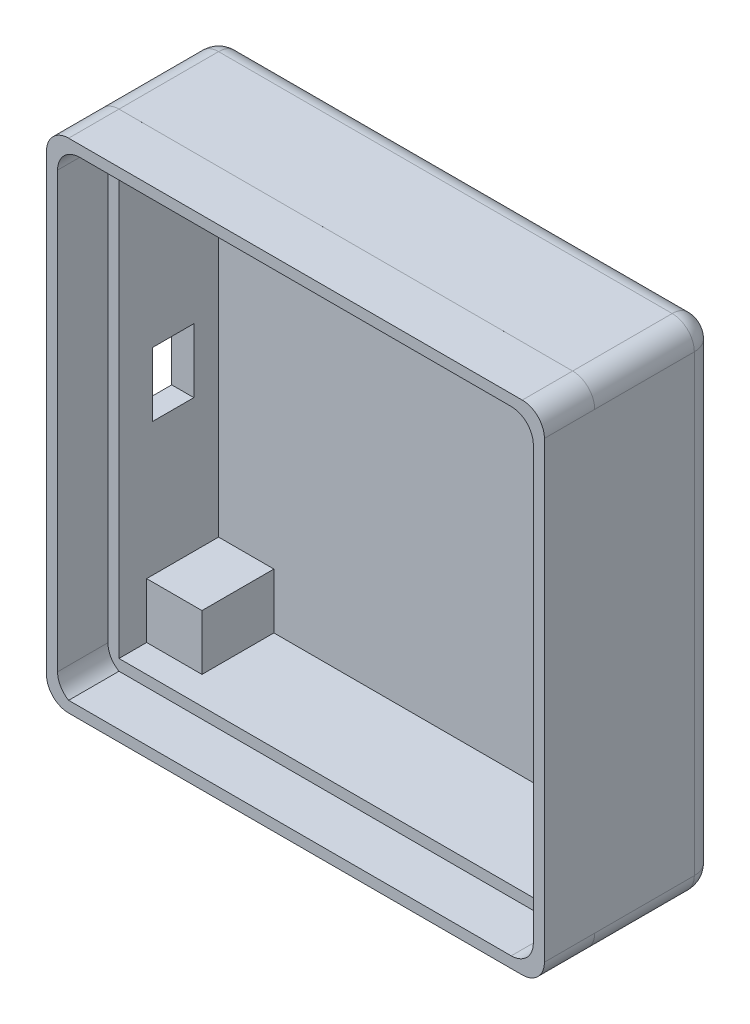
SolidWorks part; units mm, degrees
ref_plane "Piano frontale" through (0, 0, 0) normal (0, 0, 1) x (1, 0, 0)
ref_plane "Piano superiore" through (0, 0, 0) normal (0, 1, 0) x (1, 0, 0)
ref_plane "Piano destro" through (0, 0, 0) normal (1, 0, 0) x (0, 0, -1)
sketch "Schizzo2" plane through (0, 0, 0) normal (0, 0, 1) x (1, 0, 0)
  line L1 (0, 0) -> (45, 0)
  line L2 (0, 0) -> (0, 45)
  line L3 (0, 45) -> (45, 45)
  line L4 (45, 0) -> (45, 45)
  dimension "D1" = 45
  dimension "D2" = 45
extrude "Estrusione-Estrusione2" add sketch "Schizzo2" along normal blind 11
shell "Svuota1" thickness 2 removed face at (22.5, 22.5, 11)
fillet "Raccordo1" radius 2 4 edges at (45, 45, 5.5) (45, 0, 5.5) (0, 0, 5.5) (0, 45, 5.5)
fillet "Raccordo2" radius 2 8 edges at (44.4142, 0.5858, 0) (22.5, 0, 0) (0.5858, 0.5858, 0) (0, 22.5, 0) (0.5858, 44.4142, 0) (22.5, 45, 0) (44.4142, 44.4142, 0) (45, 22.5, 0)
sketch "Schizzo3" plane through (0, 0, 2) normal (0, 0, 1) x (1, 0, 0)
  line L0 (43, 43) -> (2, 43) construction
  line L1 (2, 43) -> (7, 43)
  line L2 (2, 43) -> (2, 38)
  line L3 (2, 38) -> (7, 38)
  line L4 (7, 43) -> (7, 38)
  line L5 (43, 43) -> (2, 43) construction
  dimension "D1" = 5
  dimension "D2" = 5
extrude "Estrusione-Estrusione3" add sketch "Schizzo3" along normal blind 6.5
sketch "Schizzo4" plane through (0, 0, 2) normal (0, 0, 1) x (1, 0, 0)
  line L1 (43, 2) -> (38, 2)
  line L2 (43, 2) -> (43, 7)
  line L3 (43, 7) -> (38, 7)
  line L4 (38, 2) -> (38, 7)
  dimension "D1" = 5
  dimension "D2" = 5
extrude "Estrusione-Estrusione4" add sketch "Schizzo4" along normal blind 6.5
fillet "Raccordo3" radius 4 2 edges at (38, 7, 5.25) (7, 38, 5.25)
sketch "Schizzo5" plane through (0, 0, 2) normal (0, 0, 1) x (1, 0, 0)
  line L0 (43, 2) -> (43, 43) construction
  line L1 (43, 43) -> (38, 43)
  line L2 (43, 43) -> (43, 38)
  line L3 (43, 38) -> (38, 38)
  line L4 (38, 43) -> (38, 38)
  line L5 (43, 43) -> (7, 43) construction
  line L7 (2, 2) -> (7, 2)
  line L8 (2, 2) -> (2, 7)
  line L9 (2, 7) -> (7, 7)
  line L10 (7, 2) -> (7, 7)
  dimension "D1" = 5
  dimension "D2" = 5
  dimension "D3" = 5
  dimension "D4" = 5
extrude "Estrusione-Estrusione5" add sketch "Schizzo5" along normal blind 6.5 contours L2 L1 L4 L3 | L8 L7 L10 L9
sketch "Schizzo7" plane through (0, 0, 0) normal (-1, 0, 0) x (0, 0, 1)
  line L1 (4.2347, 24.8244) -> (7.9559, 24.8244)
  line L2 (4.2347, 24.8244) -> (4.2347, 19.0329)
  line L3 (4.2347, 19.0329) -> (7.9559, 19.0329)
  line L4 (7.9559, 24.8244) -> (7.9559, 19.0329)
extrude "Taglio-Estrusione1" cut sketch "Schizzo7" against normal blind 3
sketch "Schizzo9" plane through (0, 0, 0) normal (-1, 0, 0) x (0, 0, 1)
  circle A0 centre (3.8708, 40.998) radius 1
  dimension "D1" = 2
extrude "Taglio-Estrusione2" cut sketch "Schizzo9" against normal blind 2
sketch "Schizzo12" plane through (0, 0, 11) normal (0, 0, 1) x (1, 0, 0)
  line L1 (0, 44.9999) -> (45, 44.9999)
  line L2 (0, 44.9999) -> (0, 43.9999)
  line L3 (0, 43.9999) -> (45, 43.9999)
  line L4 (45, 44.9999) -> (45, 43.9999)
  dimension "D1" = 45
  dimension "D2" = 1
extrude "Estrusione-Estrusione7" add sketch "Schizzo12" along normal blind 4.55
sketch "Schizzo13" plane through (0, 0, 11) normal (0, 0, 1) x (1, 0, 0)
  line L1 (45, 43.9999) -> (44, 43.9999)
  line L2 (45, 43.9999) -> (45, -0.0001)
  line L3 (45, -0.0001) -> (44, -0.0001)
  line L4 (44, 43.9999) -> (44, -0.0001)
  dimension "D1" = 44
  dimension "D2" = 1
extrude "Estrusione-Estrusione10" add sketch "Schizzo13" along normal blind 4.55
sketch "Schizzo15" plane through (0, 0, 11) normal (0, 0, 1) x (1, 0, 0)
  line L1 (44, -0.0001) -> (2, -0.0001)
  line L2 (44, -0.0001) -> (44, 0.9999)
  line L3 (44, 0.9999) -> (2, 0.9999)
  line L4 (2, -0.0001) -> (2, 0.9999)
  dimension "D1" = 1
  dimension "D2" = 42
extrude "Estrusione-Estrusione11" add sketch "Schizzo15" along normal blind 4.55
fillet "Raccordo4" radius 2 1 edges at (45, -0.0001, 13.275)
fillet "Raccordo5" radius 2 1 edges at (45, 44.9999, 13.275)
sketch "Schizzo17" plane through (0, 0, 11) normal (0, 0, 1) x (1, 0, 0)
  line L1 (0, 43.9999) -> (1, 43.9999)
  line L2 (0, 43.9999) -> (0, -0.0001)
  line L3 (0, -0.0001) -> (1, -0.0001)
  line L4 (1, 43.9999) -> (1, -0.0001)
  dimension "D1" = 1
  dimension "D2" = 44
extrude "Estrusione-Estrusione13" add sketch "Schizzo17" along normal blind 4.55
fillet "Raccordo6" radius 2 1 edges at (0, 44.9999, 13.275)
fillet "Raccordo7" radius 2 1 edges at (44, 0.9999, 13.275)
fillet "Raccordo8" radius 2 1 edges at (44, 43.9999, 13.275)
fillet "Raccordo9" radius 2 1 edges at (1, 43.9999, 13.275)
sketch "Schizzo18" plane through (0, 0, 11) normal (0, 0, 1) x (1, 0, 0)
  line L0 (1, -0.0001) -> (1, 41.9999) construction
  line L1 (2, -0.0001) -> (1, -0.0001)
  line L2 (2, -0.0001) -> (2, 0.9995)
  line L3 (2, 0.9995) -> (1, 0.9995)
  line L4 (1, -0.0001) -> (1, 0.9995)
extrude "Estrusione-Estrusione14" add sketch "Schizzo18" along normal blind 4.55
fillet "Raccordo10" radius 2 1 edges at (0, -0.0001, 13.275)
fillet "Raccordo11" radius 2 1 edges at (1, 0.9995, 13.275)
